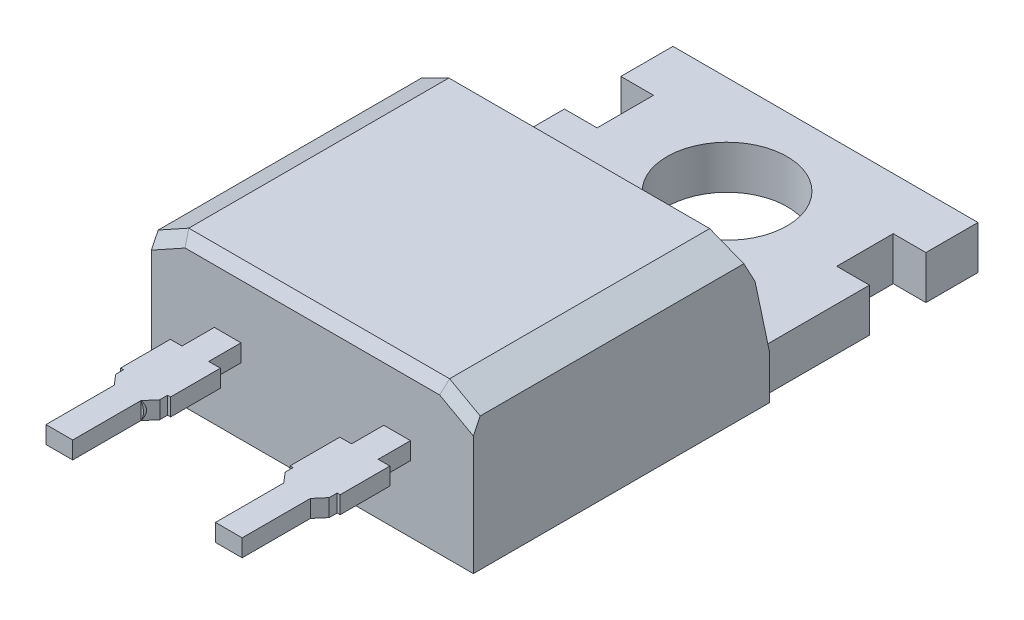
SolidWorks part; units mm, degrees
ref_plane "Front Plane" through (0, 0, 0) normal (0, 0, 1) x (1, 0, 0)
ref_plane "Top Plane" through (0, 0, 0) normal (0, 1, 0) x (1, 0, 0)
ref_plane "Right Plane" through (0, 0, 0) normal (1, 0, 0) x (0, 0, -1)
sketch "Sketch1" plane through (0, 0, 0) normal (0, 1, 0) x (1, 0, 0)
  line L0 (4.826, -1.0795) -> (-4.826, -1.0795)
  line L1 (4.826, -7.3025) -> (-4.826, -7.3025)
  line L2 (4.826, -7.3025) -> (4.826, 8.2138)
  line L3 (4.826, 7.3025) -> (-4.826, 7.3025)
  line L4 (-4.826, -7.3025) -> (-4.826, 8.2138)
  line L5 (4.826, -7.3025) -> (-4.826, 7.3025) construction
  line L6 (4.826, 7.3025) -> (-4.826, -7.3025) construction
  line L7 (4.826, -1.0795) -> (-4.826, -1.0795)
  line L8 (3.7898, 8.9789) -> (-3.7898, 8.9789)
  line L9 (-4.826, 8.2138) -> (-3.7898, 8.9789)
  line L10 (0, 7.3025) -> (0, 12.7866) construction
  line L11 (4.826, 8.2138) -> (3.7898, 8.9789)
  line L12 (4.826, 8.9789) -> (-4.826, 8.9789) construction
  point P0 (0, 0)
  dimension "D1" = 9.652
  dimension "D2" = 14.605
  dimension "D3" = 8.382
  dimension "D4" = 8.382
  dimension "D5" = 1.6764
sketch "Sketch2" plane through (0, 0, 0) normal (1, 0, 0) x (0, 0, -1)
  line L0 (14.3005, 0) -> (-1.0795, 0)
  line L1 (7.3025, 0) -> (12.7866, 0) construction
  line L2 (7.8005, 1.3) -> (7.124, 4.5)
  line L3 (7.124, 4.5) -> (-1.0795, 4.5)
  line L4 (-1.0795, 4.5) -> (-1.0795, 0)
  line L5 (14.3005, 1.3) -> (14.3005, 0)
  line L6 (14.3005, 1.3) -> (7.8005, 1.3)
  line L7 (14.3005, 1.3) -> (-7.3025, 1.3) construction
  line L8 (14.3005, 0) -> (-7.3025, 0) construction
  dimension "D1" = 4.5
  dimension "D3" = 6.5
  dimension "D2" = 15.38
extrude "Extrude1" add sketch "Sketch2" against normal up to vertex (4.826 mm away) and the other way up to vertex (4.826 mm away) up to point (-4.826, 0, 1.0795) other way up to point (4.826, 0, 1.0795)
sketch "Sketch10" plane through (0, 1.3, 0) normal (0, 1, 0) x (1, 0, 0)
  line L0 (0, 7.8005) -> (0, 16.6747) construction
  line L1 (-4.826, 7.8005) -> (4.826, 7.8005) construction
  line L2 (-4.826, 14.3005) -> (4.826, 14.3005) construction
  line L3 (-4.826, 14.3005) -> (-4.826, 7.8005) construction
  line L4 (-4.826, 12.7393) -> (-3.5922, 12.7393)
  line L5 (-4.826, 12.7393) -> (-4.826, 11.0462)
  line L6 (-4.826, 11.0462) -> (-3.5922, 11.0462)
  line L7 (-3.5922, 12.7393) -> (-3.5922, 11.0462)
  line L8 (3.5922, 12.7393) -> (3.5922, 11.0462)
  line L9 (4.826, 11.0462) -> (3.5922, 11.0462)
  line L10 (4.826, 12.7393) -> (4.826, 11.0462)
  line L11 (4.826, 12.7393) -> (3.5922, 12.7393)
  circle A0 centre (0, 11.3505) radius 1.8
  dimension "D1" = 3.6
  dimension "D2" = 2.95
extrude "Extrude5" cut sketch "Sketch10" against normal through all
sketch "Sketch6" plane through (0, 0, 1.0795) normal (0, 0, 1) x (1, 0, 0)
  line L0 (0, 4.5) -> (0, 0) construction
  line L1 (-4.826, 4.5) -> (4.826, 4.5) construction
  line L2 (-2.54, 4.5) -> (-2.54, 0) construction
  line L3 (2.54, 4.5) -> (2.54, 0) construction
  line L4 (-4.826, 2.25) -> (4.826, 2.25) construction
  line L5 (-4.826, 4.5) -> (-4.826, 0) construction
  line L6 (4.826, 4.5) -> (4.826, 0) construction
  line L7 (2.14, 2.51) -> (2.94, 2.51)
  line L8 (-2.94, 2.51) -> (-2.14, 2.51)
  line L9 (-2.94, 2.51) -> (-2.94, 1.99)
  line L10 (-2.94, 1.99) -> (-2.14, 1.99)
  line L11 (-2.14, 2.51) -> (-2.14, 1.99)
  line L12 (-2.94, 2.51) -> (-2.14, 1.99) construction
  line L13 (-2.94, 1.99) -> (-2.14, 2.51) construction
  line L14 (2.14, 2.51) -> (2.14, 1.99)
  line L15 (2.14, 1.99) -> (2.94, 1.99)
  line L16 (2.94, 2.51) -> (2.94, 1.99)
  line L17 (2.14, 2.51) -> (2.94, 1.99) construction
  line L18 (2.14, 1.99) -> (2.94, 2.51) construction
  line L19 (-0.4, 2.51) -> (0.4, 2.51)
  line L20 (-0.4, 2.51) -> (-0.4, 1.99)
  line L21 (-0.4, 1.99) -> (0.4, 1.99)
  line L22 (0.4, 2.51) -> (0.4, 1.99)
  line L23 (-0.4, 2.51) -> (0.4, 1.99) construction
  line L24 (-0.4, 1.99) -> (0.4, 2.51) construction
  point P15 (-2.54, 2.25)
  point P21 (2.54, 2.25)
  point P26 (0, 2.25)
  dimension "D3" = 0.8
  dimension "D4" = 0.52
  dimension "D5" = 0.8
  dimension "D6" = 0.8
  dimension "D1" = 2.54
  dimension "D2" = 2.54
extrude "Extrude6" add sketch "Sketch6" along normal blind 13
sketch "Sketch11" plane through (0, 2.51, 0) normal (0, 1, 0) x (1, 0, 0)
  line L0 (-2.94, -7.5795) -> (-2.14, -7.5795) construction
  line L1 (-2.94, -14.0795) -> (-2.94, -1.0795) construction
  line L2 (-2.14, -14.0795) -> (-2.14, -1.0795) construction
  line L3 (-2.54, -7.5795) -> (-2.54, 1.2721) construction
  line L4 (-4.826, -1.0795) -> (4.826, -1.0795) construction
  line L5 (-3.29, -2.0475) -> (-1.79, -2.0475)
  line L6 (-3.29, -2.0475) -> (-3.29, -3.5395)
  line L7 (-2.94, -4.0795) -> (-2.14, -4.0795)
  line L8 (-1.8796, -3.7747) -> (-1.8796, -3.5395)
  line L9 (-3.29, -2.0475) -> (-1.869, -4.1434) construction
  line L10 (-3.1272, -4.0199) -> (-1.79, -2.0475) construction
  line L11 (-3.29, -3.5395) -> (-3.2004, -3.5395)
  line L12 (-0.75, -2.0475) -> (0.75, -2.0475)
  line L13 (-2.14, -4.0795) -> (-1.8796, -3.7747)
  line L14 (-2.94, -4.0795) -> (-3.2004, -3.7747)
  line L15 (-3.2004, -3.7747) -> (-3.2004, -3.5395)
  line L16 (-1.79, -3.5395) -> (-1.8796, -3.5395)
  line L17 (-1.79, -2.0475) -> (-1.79, -3.5395)
  line L18 (-0.75, -2.0475) -> (-0.75, -3.5395)
  line L19 (-0.4, -4.0795) -> (0.4, -4.0795)
  line L20 (0.6604, -3.7747) -> (0.6604, -3.5395)
  line L21 (-0.75, -3.5395) -> (-0.6604, -3.5395)
  line L22 (0.4, -4.0795) -> (0.6604, -3.7747)
  line L23 (-0.4, -4.0795) -> (-0.6604, -3.7747)
  line L24 (-0.6604, -3.7747) -> (-0.6604, -3.5395)
  line L25 (0.75, -3.5395) -> (0.6604, -3.5395)
  line L26 (0.75, -2.0475) -> (0.75, -3.5395)
  line L27 (-0.75, -2.0475) -> (0.671, -4.1434) construction
  line L28 (-0.5872, -4.0199) -> (0.75, -2.0475) construction
  line L29 (1.79, -2.0475) -> (3.29, -2.0475)
  line L30 (1.79, -2.0475) -> (1.79, -3.5395)
  line L31 (2.14, -4.0795) -> (2.94, -4.0795)
  line L32 (3.2004, -3.7747) -> (3.2004, -3.5395)
  line L33 (1.79, -3.5395) -> (1.8796, -3.5395)
  line L34 (2.94, -4.0795) -> (3.2004, -3.7747)
  line L35 (2.14, -4.0795) -> (1.8796, -3.7747)
  line L36 (1.8796, -3.7747) -> (1.8796, -3.5395)
  line L37 (3.29, -3.5395) -> (3.2004, -3.5395)
  line L38 (3.29, -2.0475) -> (3.29, -3.5395)
  line L39 (1.79, -2.0475) -> (3.211, -4.1434) construction
  line L40 (1.9528, -4.0199) -> (3.29, -2.0475) construction
  point P8 (-2.54, -3.1537)
  point P15 (0, -3.1537)
  point P25 (-2.54, -4.0795)
  point P27 (-2.54, -2.0475)
  point P38 (0, -4.0795)
  point P40 (0, -2.0475)
  point P41 (2.54, -3.1537)
  point P53 (2.54, -4.0795)
  point P55 (2.54, -2.0475)
  dimension "D1" = 2.032
  dimension "D2" = 3
  dimension "D3" = 2.46
  dimension "D5" = 1.5
  dimension "D6" = 0.3048
  dimension "D4" = 1.3208
extrude "Extrude7" add sketch "Sketch11" against normal up to vertex (0.52 mm away) up to point (-2.94, 1.99, 14.0795)
chamfer "Chamfer1" distance 0.254 angle 45 6 edges at (2.94, 2.25, 14.0795) (2.14, 2.25, 14.0795) (0.4, 2.25, 14.0795) (-0.4, 2.25, 14.0795) (-2.14, 2.25, 14.0795) (-2.94, 2.25, 14.0795)
sketch "Sketch12" plane through (-4.826, 0, 0) normal (-1, 0, 0) x (0, 0, 1)
  line L0 (1.0795, 0) -> (-11.0462, 0) construction
  line L1 (-15.1802, 2.7361) -> (-7.8005, 2.7361)
  line L2 (-15.1802, 2.7361) -> (-15.1802, 0)
  line L3 (-15.1802, 0) -> (-7.8005, 0)
  line L4 (-7.8005, 2.7361) -> (-7.8005, 0)
extrude "Extrude8" cut sketch "Sketch12" against normal blind 0.254
sketch "Sketch13" plane through (4.826, 0, 0) normal (1, 0, 0) x (0, 0, -1)
  line L4 (15.1802, 2.7361) -> (7.8005, 2.7361)
  line L5 (7.8005, 2.7361) -> (7.8005, 0)
  line L6 (7.8005, 0) -> (15.1802, 0)
  line L7 (15.1802, 0) -> (15.1802, 2.7361)
  line L8 (15.1802, 2.7361) -> (7.8005, 2.7361)
  line L9 (7.8005, 2.7361) -> (7.8005, 0)
  line L10 (7.8005, 0) -> (15.1802, 0)
  line L11 (15.1802, 0) -> (15.1802, 2.7361)
  dimension "D1" = 0
extrude "Extrude9" cut sketch "Sketch13" against normal blind 0.254
chamfer "Chamfer2" distance 0.508 angle 61 2 edges at (4.826, 4.5, -3.0223) (-4.826, 4.5, -3.0223) first distance on face at (4.826, 2.06, -4.1132) first distance on face at (-4.826, 2.06, -4.1132)
chamfer "Chamfer3" distance 0.2032 angle 61 6 edges at (4.3678, 4.246, 1.0795) (0, 4.5, 1.0795) (-4.3678, 4.246, 1.0795) (4.3678, 4.246, -7.1777) (0, 4.5, -7.124) (-4.3678, 4.246, -7.1777) first distance on face at (4.3678, 4.246, -3.0491) first distance on face at (0, 4.5, -3.0223) first distance on face at (-4.3678, 4.246, -3.0491)
ref_plane "Plane1" through (0, 0, 4.0795) normal (0, 0, 1) x (1, 0, 0)
sketch "Sketch15" plane through (0, 0, 4.0795) normal (0, 0, 1) x (1, 0, 0)
  line L0 (-2.14, 2.51) -> (-2.94, 2.51) construction
  line L1 (-2.14, 2.51) -> (-2.94, 2.51)
  line L2 (-2.94, 1.99) -> (-2.14, 1.99) construction
  line L3 (-2.94, 1.99) -> (-2.14, 1.99)
  arc A0 (-2.14, 1.99) -> (-2.14, 2.51) centre (-2.54, 2.25) ccw
  arc A1 (-2.94, 2.51) -> (-2.94, 1.99) centre (-2.54, 2.25) ccw
extrude "Extrude10" add sketch "Sketch15" against normal blind 1.016
sketch "Esboço1" plane through (0, 2.51, 0) normal (0, 1, 0) x (1, 0, 0)
  line L0 (3.8147, -1.0795) -> (-3.8147, -1.0795) construction
  line L1 (-1.2077, -15.1023) -> (1.3006, -15.1023)
  line L2 (-1.2077, -15.1023) -> (-1.2077, -1.0795)
  line L3 (-1.2077, -1.0795) -> (1.3006, -1.0795)
  line L4 (1.3006, -15.1023) -> (1.3006, -1.0795)
extrude "Corte-extrusão1" cut sketch "Esboço1" against normal blind 2.54
ref_axis "Axis1" through (0, -6.4599, -11.3505) along (0, 1, 0)
ref_plane "Plane2" through (0, 0, -11.3505) normal (0, 0, 1) x (1, 0, 0)
ref_plane "Plane3" through (0, 0, 6.1245) normal (0, 0, 1) x (1, 0, 0)
ref_plane "Plane4" through (0, 2.25, 0) normal (0, 1, 0) x (1, 0, 0)
ref_plane "Plane5" through (0, 0, 3.6495) normal (0, 0, 1) x (1, 0, 0)
sketch "Sketch17" plane through (0, 0, 6.1245) normal (0, 0, 1) x (1, 0, 0)
  line L1 (-7.4922, -6.2131) -> (7.4922, -6.2131)
  line L2 (-7.4922, -6.2131) -> (-7.4922, 6.2131)
  line L3 (-7.4922, 6.2131) -> (7.4922, 6.2131)
  line L4 (7.4922, -6.2131) -> (7.4922, 6.2131)
  line L5 (-7.4922, -6.2131) -> (7.4922, 6.2131) construction
  line L6 (-7.4922, 6.2131) -> (7.4922, -6.2131) construction
  point P0 (0, 0)
extrude "Cut-Extrude1" cut sketch "Sketch17" along normal through all
ref_plane "Plane6" through (-2.54, 0, 0) normal (-1, 0, 0) x (0, 0, 1)
ref_plane "Plane7" through (2.54, 0, 0) normal (-1, 0, 0) x (0, 0, 1)
